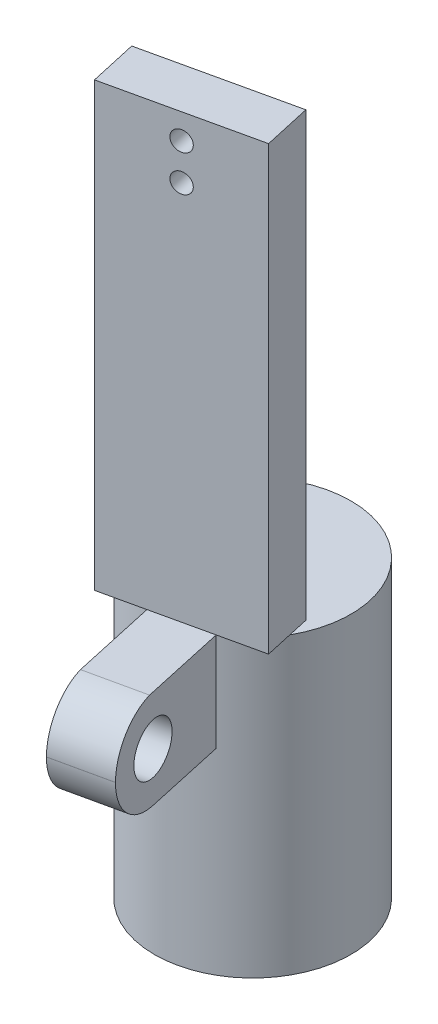
SolidWorks part; units mm, degrees
material "ABS"
ref_plane "Спереди" through (0, 0, 0) normal (0, 0, 1) x (1, 0, 0)
ref_plane "Сверху" through (0, 0, 0) normal (0, 1, 0) x (1, 0, 0)
ref_plane "Справа" through (0, 0, 0) normal (1, 0, 0) x (0, 0, -1)
sketch "Эскиз2" plane through (0, 0, 0) normal (0, 1, 0) x (1, 0, 0)
  circle A0 centre (0, 0) radius 10
  dimension "D1" = 20
extrude "Бобышка-Вытянуть1" add sketch "Эскиз2" along normal blind 30
sketch "Эскиз3" plane through (0, 30, 0) normal (0, 1, 0) x (1, 0, 0)
  line L0 (-9.7663, -2.1493) -> (9.7663, 2.1493) construction
  line L1 (-10.6757, -2.1493) -> (-146.1068, -29.4158) construction
  circle A0 centre (0, 0) radius 10 construction
sketch "Эскиз4" plane through (0, 30, 0) normal (0, 1, 0) x (1, 0, 0)
  line L0 (2.1821, -9.759) -> (-2.1166, 9.7734) construction
  line L1 (4.9653, -8.6802) -> (0.8623, 9.9627)
  line L2 (-9.7663, -2.1493) -> (9.7663, 2.1493) construction
  line L3 (-0.7924, -9.9686) -> (-4.9042, 8.7149)
  line L4 (4.9653, -8.6802) -> (7.8573, -21.8211)
  line L5 (7.8573, -21.8211) -> (2.0952, -23.0892)
  line L6 (-0.7924, -9.9686) -> (2.0952, -23.0892)
  circle A0 centre (0, 0) radius 10 construction
  circle A1 centre (0.0327, 0.0072) radius 9.9665
  circle M9 centre (0, 0) radius 10
  dimension "D1" = 2.95
  dimension "D2" = 2.95
  dimension "D3" = 13
extrude "Бобышка-Вытянуть2" add sketch "Эскиз4" against normal blind 10 contours L6 L5 L4 M9 region at (3.564, 30, 16.0345)
sketch "Эскиз6" plane through (2.9138, 0, -0.6413) normal (0.9766, 0, -0.2149) x (-0.2149, 0, -0.9766)
  line L0 (-22.9999, 20) -> (-22.9999, 30)
  line L1 (-22.9999, 30) -> (-9.5446, 30)
  line L2 (-9.5446, 30) -> (-22.9999, 30) construction
  line L3 (-9.5446, 20) -> (-9.5446, 30) construction
  line L4 (-9.5446, 30) -> (-9.5446, 20)
  line L5 (-9.5446, 20) -> (-22.9999, 20)
  line L6 (-22.9999, 25.014) -> (-9.5446, 25) construction
  circle A1 centre (-17.9875, 25.0088) radius 5.0124
  circle A2 centre (-17.9875, 25.0088) radius 2.55
  line M6 (-9.5446, 30) -> (-22.9999, 30)
  line M7 (-22.9999, 30) -> (-22.9999, 20)
  line M8 (-22.9999, 20) -> (-9.5446, 20)
extrude "Вырез-Вытянуть4" cut sketch "Эскиз6" against normal through all contours A1 L0 M8 region at (7.6176, 21.1197, 20.732)
extrude "Вырез-Вытянуть5" cut sketch "Эскиз6<3>" against normal through all contours A1 M6 M7 region at (7.6216, 28.8807, 20.7504)
sketch "Эскиз6<3>" plane through (2.9138, 0, -0.6413) normal (0.9766, 0, -0.2149) x (-0.2149, 0, -0.9766) same geometry as "Эскиз6"
extrude "Вырез-Вытянуть6" cut sketch "Эскиз6<4>" against normal through all contours L6 A2 region at (6.7802, 23.9265, 16.9269)
sketch "Эскиз6<4>" plane through (2.9138, 0, -0.6413) normal (0.9766, 0, -0.2149) x (-0.2149, 0, -0.9766) same geometry as "Эскиз6"
extrude "Вырез-Вытянуть7" cut sketch "Эскиз6<5>" against normal through all contours A2 L6 region at (6.7797, 26.091, 16.9247)
sketch "Эскиз6<5>" plane through (2.9138, 0, -0.6413) normal (0.9766, 0, -0.2149) x (-0.2149, 0, -0.9766) same geometry as "Эскиз6"
sketch "Эскиз9" plane through (0, 0, 0) normal (0, -1, 0) x (-1, 0, 0)
  line L0 (9.901, -1.4033) -> (7.8327, -11.6956)
  line L1 (9.901, -1.4033) -> (-9.5754, 2.8831) construction
  line L2 (7.8327, -11.6956) -> (7.2779, -14.4562)
  line L3 (9.7663, -2.1493) -> (-9.7663, 2.1493) construction
  circle A0 centre (0, 0) radius 10 construction
sketch "Эскиз10" plane through (0, 0, 0) normal (0, -1, 0) x (1, 0, 0)
  line L1 (-9.7663, 2.1493) -> (9.7663, -2.1493) construction
  circle A0 centre (0, 0) radius 5.05
  dimension "D1" = 10.1
extrude "Вырез-Вытянуть8" cut sketch "Эскиз10" against normal blind 25
sketch "Эскиз11" plane through (0, 30, 0) normal (0, 1, 0) x (1, 0, 0)
  line L0 (4.9653, -8.6802) -> (-0.7924, -9.9686) construction
  line L1 (2.0864, -9.3244) -> (1.2741, -5.6939) construction
  line L2 (-0.7924, -9.9686) -> (-5.1546, -10.9446)
  line L3 (4.9653, -8.6802) -> (9.3275, -7.7041)
  line L4 (-5.1546, -10.9446) -> (-6.2464, -6.0653)
  line L5 (-6.2464, -6.0653) -> (9.6822, -2.5011)
  line L6 (9.3275, -7.7041) -> (8.2357, -2.8248)
  line L7 (4.9653, -8.6802) -> (-0.7924, -9.9686)
  arc A0 (4.9653, -8.6802) -> (-0.7924, -9.9686) centre (0, 0) ccw construction
  arc M6 (4.9653, -8.6802) -> (-0.7924, -9.9686) centre (0, 0) ccw
  dimension "D1" = 5
extrude "Бобышка-Вытянуть3" add sketch "Эскиз11" along normal blind 45 contours L7 L6 L5 L4 M6 | L4 L2 M6 | L3 L6 M6 region at (1.4835, 30, 6.6298) region at (-4.0509, 30, 9.8141) region at (7.8472, 30, 7.1518)
sketch "Эскиз12" plane through (2.0864, 0, 9.3244) normal (0.2184, 0, 0.9759) x (0.9759, 0, -0.2184)
  line L0 (0, 75) -> (0, 30) construction
  line L1 (7.4201, 75) -> (-7.4201, 75) construction
  line L2 (2.95, 30) -> (-2.95, 30) construction
  circle A0 centre (0, 72.4261) radius 1
  circle A1 centre (0, 68.7355) radius 1
  point P10 (0, 0)
extrude "Вырез-Вытянуть9" cut sketch "Эскиз12" against normal through all
